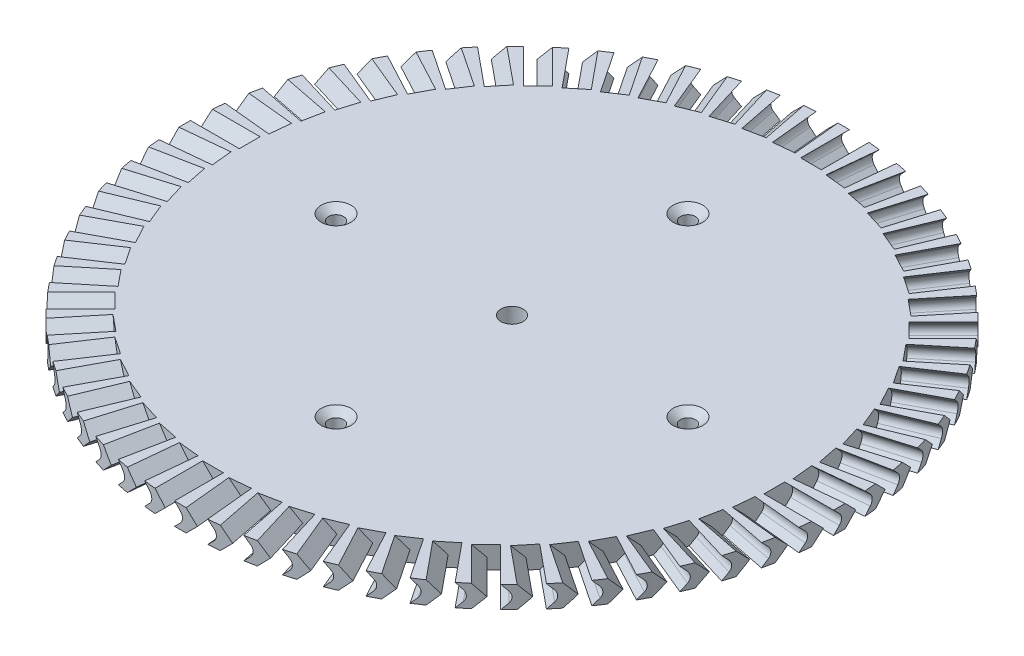
SolidWorks part; units mm, degrees
material "AISI 316 Annealed Stainless Steel Bar (SS)"
ref_plane "Front Plane" through (0, 0, 0) normal (0, 0, 1) x (1, 0, 0)
ref_plane "Top Plane" through (0, 0, 0) normal (0, 1, 0) x (1, 0, 0)
ref_plane "Right Plane" through (0, 0, 0) normal (1, 0, 0) x (0, 0, -1)
sketch "Sketch1" plane through (0, 0, 0) normal (0, 1, 0) x (1, 0, 0)
  circle A0 centre (0, 0) radius 4.7625
  circle A1 centre (0, 0) radius 142.7035
  point P4 (0, 0)
  point P15 (0, 0)
  dimension "D1" = 9.525
  dimension "D2" = 285.4071
extrude "Boss-Extrude1" add sketch "Sketch1" along normal blind 9.525
ref_plane "Plane1" through (0, 0, 142.7035) normal (0, 0, 1) x (1, 0, 0)
sketch "Sketch2" plane through (0, 0, 142.7035) normal (0, 0, 1) x (1, 0, 0)
  line L4 (-0.9299, 2.5174) -> (-3.4474, 0)
  line L5 (-142.7035, 0) -> (142.7035, 0) construction
  line L6 (-0.9299, 7.0076) -> (-3.4474, 9.525)
  line L9 (142.7035, 9.525) -> (-142.7035, 9.525) construction
  line L10 (-5.4201, 2.5174) -> (-12.4276, 9.525)
  line L11 (-5.4201, 7.0076) -> (-12.4276, 0)
  line L12 (-12.4276, 9.525) -> (-3.4474, 9.525)
  line L13 (-12.4276, 0) -> (-3.4474, 0)
  line L14 (0, 0) -> (0, 9.525) construction
  line L15 (4.7625, 9.525) -> (-4.7625, 9.525) construction
  line L16 (-3.175, 4.7625) -> (0, 4.7625) construction
  circle A0 centre (-3.175, 4.7625) radius 3.175
  point P19 (0, 4.7625)
  dimension "D1" = 6.35
  dimension "D2" = 45
  dimension "D3" = 45
extrude "Cut-Extrude1" cut sketch "Sketch2" against normal blind 21.1582 contours A0 | A0 L6 L12 L10 L11 | A0 L11 L10 | A0 L10 L11 L13 L4 region at (-7.2864, 1.5647, 142.7035) region at (-3.175, 4.7625, 142.7035) region at (-6.6622, 4.7625, 142.7035) region at (-7.2864, 7.9603, 142.7035)
pattern_circular "CirPattern1" count 64 over 360 about axis through (0, 9.525, 0) along (0, -1, 0) of "Cut-Extrude1" reverse direction yes
hole_wizard "CSK for 1/4 Flat Head Machine Screw (100)1" positions "3DSketch1" profile "Sketch3" countersink size "1/4" standard "ANSI Inch"
sketch3d "3DSketch1"
  line L0 (0, 0, 0) -> (0, 0, 76.2) construction
  point P0 (0, 9.525, 76.2)
  point P7 (0, 0, 86.7106)
  point P8 (0, 0, 0)
sketch "Sketch3" plane through (0, 9.525, 76.2) normal (1, 0, 0) x (0, 0, 1)
  line L0 (0, 0) -> (0, 14.6611)
  line L1 (0, 14.6611) -> (3.2639, 12.7)
  line L2 (3.2639, 12.7) -> (3.2639, 2.6641)
  line L3 (3.2639, 2.6641) -> (6.4389, 0)
  line L5 (6.4389, 0) -> (0, 0)
  line L6 (-3.2639, 2.6641) -> (-6.4389, 0) construction
  line L10 (0, 14.6611) -> (-3.2639, 12.7) construction
  line L11 (0, -6.35) -> (0, 107.95) construction
  dimension "Hole Dia." = 6.5278
  dimension "Hole Depth" = 12.7
  dimension "Near C'Sink Dia." = 12.8778
  dimension "Near C'Sink Angle" = 100
  dimension "Drill Angle" = 118
pattern_circular "CirPattern2" count 4 over 360 about axis through (0, 9.525, 0) along (0, -1, 0) of "CSK for 1/4 Flat Head Machine Screw (100)1" reverse direction yes
